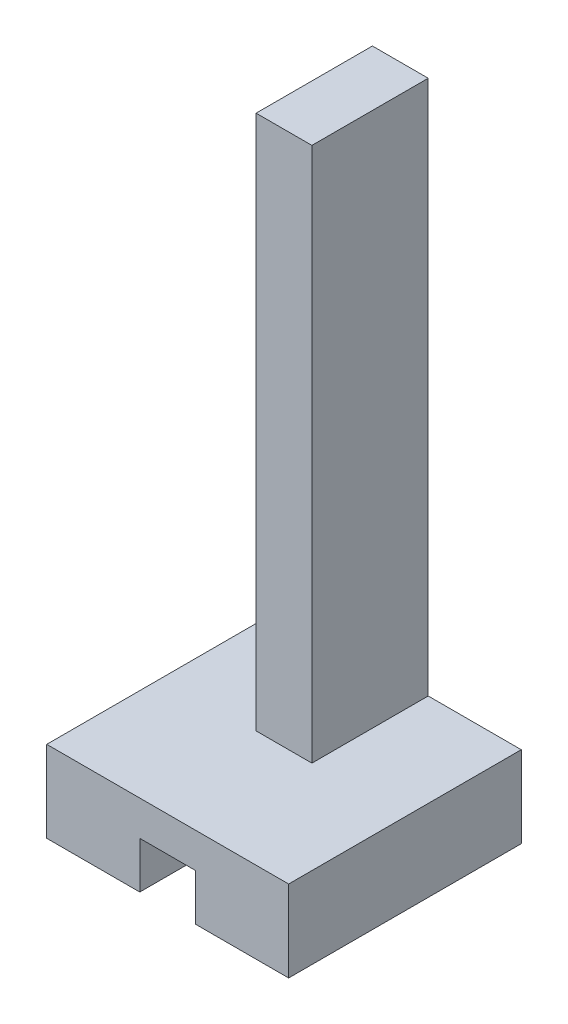
SolidWorks part; units mm, degrees
ref_plane "Ebene vorne" through (0, 0, 0) normal (0, 0, 1) x (1, 0, 0)
ref_plane "Ebene oben" through (0, 0, 0) normal (0, 1, 0) x (1, 0, 0)
ref_plane "Ebene rechts" through (0, 0, 0) normal (1, 0, 0) x (0, 0, -1)
sketch "Skizze1" plane through (0, 0, 0) normal (0, 0, 1) x (1, 0, 0)
  line L1 (0, 0) -> (1040, 0)
  line L2 (0, 0) -> (0, 350)
  line L3 (0, 350) -> (1040, 350)
  line L4 (1040, 0) -> (1040, 350)
  dimension "D1" = 1040
  dimension "D2" = 350
extrude "Aufsatz-Linear austragen1" add sketch "Skizze1" along normal blind 1000
sketch "Skizze2" plane through (0, 0, 1000) normal (0, 0, 1) x (1, 0, 0)
  line L0 (0, 0) -> (1040, 0) construction
  line L1 (400, 0) -> (640, 0)
  line L2 (400, 0) -> (400, 200)
  line L3 (400, 200) -> (640, 200)
  line L4 (640, 0) -> (640, 200)
  line L5 (0, 350) -> (0, 0) construction
  line L6 (1040, 0) -> (1040, 350) construction
  dimension "D1" = 400
  dimension "D2" = 400
  dimension "D3" = 200
extrude "Schnitt-Linear austragen1" cut sketch "Skizze2" against normal through all
sketch "Skizze3" plane through (0, 350, 0) normal (0, 1, 0) x (1, 0, 0)
  line L0 (1040, 0) -> (0, 0) construction
  line L1 (400, 0) -> (640, 0)
  line L2 (400, 0) -> (400, -500)
  line L3 (400, -500) -> (640, -500)
  line L4 (640, 0) -> (640, -500)
  line L5 (1040, -1000) -> (1040, 0) construction
  line L6 (0, -1000) -> (0, 0) construction
  dimension "D1" = 500
  dimension "D2" = 400
  dimension "D3" = 400
extrude "Aufsatz-Linear austragen2" add sketch "Skizze3" along normal blind 2300
